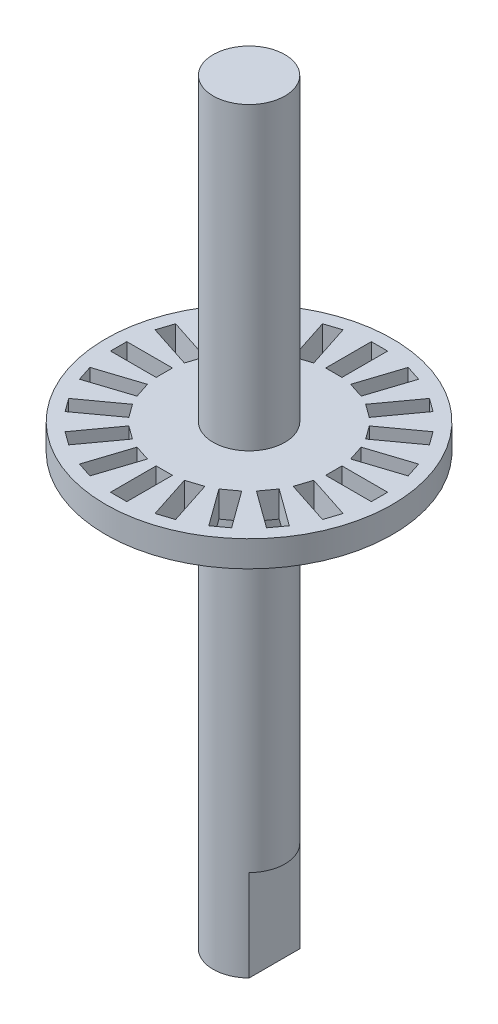
SolidWorks part; units mm, degrees
ref_plane "前视基准面" through (0, 0, 0) normal (0, 0, 1) x (1, 0, 0)
ref_plane "上视基准面" through (0, 0, 0) normal (0, 1, 0) x (1, 0, 0)
ref_plane "右视基准面" through (0, 0, 0) normal (1, 0, 0) x (0, 0, -1)
sketch "草图1" plane through (0, 0, 0) normal (0, 1, 0) x (1, 0, 0)
  circle A0 centre (0, 0) radius 2.75
  dimension "D1" = 5.5
extrude "凸台-拉伸1" add sketch "草图1" along normal blind 51
sketch "草图2" plane through (0, 0, 0) normal (0, -1, 0) x (1, 0, 0)
  line L0 (0, 0) -> (0, -4.8851) construction
  line L2 (-1.95, 1.9391) -> (-1.95, -1.9391)
  line L4 (1.95, 1.9391) -> (1.95, -1.9391)
  arc A0 (-1.95, -1.9391) -> (1.95, -1.9391) centre (0, 0) ccw
  arc A1 (1.95, 1.9391) -> (-1.95, 1.9391) centre (0, 0) ccw
  dimension "D1" = 5.5
  dimension "D2" = 3.9
extrude "凸台-拉伸2" add sketch "草图2" along normal blind 7
sketch "草图6" plane through (0, 51, 0) normal (0, 1, 0) x (1, 0, 0)
  line L2 (0, 11) -> (0, 0) construction
  line L3 (2.4958, 9.7037) -> (3.6846, 9.3174)
  line L42 (-0.625, 10) -> (0.625, 10)
  line L43 (-0.625, 10) -> (-0.625, 6.5)
  line L44 (-0.625, 6.5) -> (0.625, 6.5)
  line L45 (0.625, 10) -> (0.625, 6.5)
  line L46 (2.4958, 9.7037) -> (1.4142, 6.375)
  line L47 (1.4142, 6.375) -> (2.603, 5.9887)
  line L48 (3.6846, 9.3174) -> (2.603, 5.9887)
  line L49 (5.3722, 8.4575) -> (6.3835, 7.7228)
  line L50 (5.3722, 8.4575) -> (3.315, 5.626)
  line L51 (3.315, 5.626) -> (4.3262, 4.8912)
  line L52 (6.3835, 7.7228) -> (4.3262, 4.8912)
  line L53 (7.7228, 6.3835) -> (8.4575, 5.3722)
  line L54 (7.7228, 6.3835) -> (4.8912, 4.3262)
  line L55 (4.8912, 4.3262) -> (5.626, 3.315)
  line L56 (8.4575, 5.3722) -> (5.626, 3.315)
  line L57 (9.3174, 3.6846) -> (9.7037, 2.4958)
  line L58 (9.3174, 3.6846) -> (5.9887, 2.603)
  line L59 (5.9887, 2.603) -> (6.375, 1.4142)
  line L60 (9.7037, 2.4958) -> (6.375, 1.4142)
  line L61 (10, 0.625) -> (10, -0.625)
  line L62 (10, 0.625) -> (6.5, 0.625)
  line L63 (6.5, 0.625) -> (6.5, -0.625)
  line L64 (10, -0.625) -> (6.5, -0.625)
  line L65 (9.7037, -2.4958) -> (9.3174, -3.6846)
  line L66 (9.7037, -2.4958) -> (6.375, -1.4142)
  line L67 (6.375, -1.4142) -> (5.9887, -2.603)
  line L68 (9.3174, -3.6846) -> (5.9887, -2.603)
  line L69 (8.4575, -5.3722) -> (7.7228, -6.3835)
  line L70 (8.4575, -5.3722) -> (5.626, -3.315)
  line L71 (5.626, -3.315) -> (4.8912, -4.3262)
  line L72 (7.7228, -6.3835) -> (4.8912, -4.3262)
  line L73 (6.3835, -7.7228) -> (5.3722, -8.4575)
  line L74 (6.3835, -7.7228) -> (4.3262, -4.8912)
  line L75 (4.3262, -4.8912) -> (3.315, -5.626)
  line L76 (5.3722, -8.4575) -> (3.315, -5.626)
  line L77 (3.6846, -9.3174) -> (2.4958, -9.7037)
  line L78 (3.6846, -9.3174) -> (2.603, -5.9887)
  line L79 (2.603, -5.9887) -> (1.4142, -6.375)
  line L80 (2.4958, -9.7037) -> (1.4142, -6.375)
  line L81 (0.625, -10) -> (-0.625, -10)
  line L82 (0.625, -10) -> (0.625, -6.5)
  line L83 (0.625, -6.5) -> (-0.625, -6.5)
  line L84 (-0.625, -10) -> (-0.625, -6.5)
  line L85 (-2.4958, -9.7037) -> (-3.6846, -9.3174)
  line L86 (-2.4958, -9.7037) -> (-1.4142, -6.375)
  line L87 (-1.4142, -6.375) -> (-2.603, -5.9887)
  line L88 (-3.6846, -9.3174) -> (-2.603, -5.9887)
  line L89 (-5.3722, -8.4575) -> (-6.3835, -7.7228)
  line L90 (-5.3722, -8.4575) -> (-3.315, -5.626)
  line L91 (-3.315, -5.626) -> (-4.3262, -4.8912)
  line L92 (-6.3835, -7.7228) -> (-4.3262, -4.8912)
  line L93 (-7.7228, -6.3835) -> (-8.4575, -5.3722)
  line L94 (-7.7228, -6.3835) -> (-4.8912, -4.3262)
  line L95 (-4.8912, -4.3262) -> (-5.626, -3.315)
  line L96 (-8.4575, -5.3722) -> (-5.626, -3.315)
  line L97 (-9.3174, -3.6846) -> (-9.7037, -2.4958)
  line L98 (-9.3174, -3.6846) -> (-5.9887, -2.603)
  line L99 (-5.9887, -2.603) -> (-6.375, -1.4142)
  line L100 (-9.7037, -2.4958) -> (-6.375, -1.4142)
  line L101 (-10, -0.625) -> (-10, 0.625)
  line L102 (-10, -0.625) -> (-6.5, -0.625)
  line L103 (-6.5, -0.625) -> (-6.5, 0.625)
  line L104 (-10, 0.625) -> (-6.5, 0.625)
  line L105 (-9.7037, 2.4958) -> (-9.3174, 3.6846)
  line L106 (-9.7037, 2.4958) -> (-6.375, 1.4142)
  line L107 (-6.375, 1.4142) -> (-5.9887, 2.603)
  line L108 (-9.3174, 3.6846) -> (-5.9887, 2.603)
  line L109 (-8.4575, 5.3722) -> (-7.7228, 6.3835)
  line L110 (-8.4575, 5.3722) -> (-5.626, 3.315)
  line L111 (-5.626, 3.315) -> (-4.8912, 4.3262)
  line L112 (-7.7228, 6.3835) -> (-4.8912, 4.3262)
  line L113 (-6.3835, 7.7228) -> (-5.3722, 8.4575)
  line L114 (-6.3835, 7.7228) -> (-4.3262, 4.8912)
  line L115 (-4.3262, 4.8912) -> (-3.315, 5.626)
  line L116 (-5.3722, 8.4575) -> (-3.315, 5.626)
  line L117 (-3.6846, 9.3174) -> (-2.4958, 9.7037)
  line L118 (-3.6846, 9.3174) -> (-2.603, 5.9887)
  line L119 (-2.603, 5.9887) -> (-1.4142, 6.375)
  line L120 (-2.4958, 9.7037) -> (-1.4142, 6.375)
  circle A0 centre (0, 0) radius 11
  point P88 (0, 0)
  dimension "D1" = 22
  dimension "D3" = 10
  dimension "D4" = 6.5
  dimension "D2" = 1.25
extrude "凸台-拉伸4" add sketch "草图6" along normal blind 2 from offset 25 offset against normal yes
